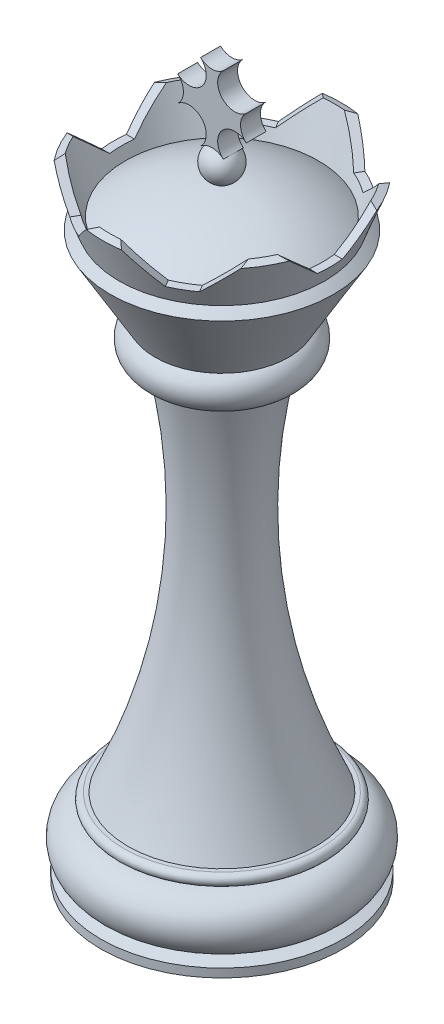
SolidWorks part; units mm, degrees
ref_plane "Front Plane" through (0, 0, 0) normal (0, 0, 1) x (1, 0, 0)
ref_plane "Top Plane" through (0, 0, 0) normal (0, 1, 0) x (1, 0, 0)
ref_plane "Right Plane" through (0, 0, 0) normal (1, 0, 0) x (0, 0, -1)
sketch "Sketch1" plane through (0, 0, 0) normal (0, 0, 1) x (1, 0, 0)
  line L0 (0, 0) -> (0, -19.2438) construction
  line L1 (0, 0) -> (12.5016, 0)
  line L2 (12.4781, -1.4284) -> (12.4781, -1.4919)
  line L3 (0, -9.6219) -> (15.4504, -9.6219)
  line L4 (15.4504, -9.6219) -> (15.4504, -8.5301)
  line L5 (15.4504, -8.5301) -> (13.8939, -8.0177)
  line L6 (0, 0) -> (0, -9.6219)
  line L7 (0, -9.6219) -> (0, 67.4601) construction
  line L8 (14.3355, 68.8883) -> (12.3128, 63.5994)
  line L9 (14.2366, 62.0928) -> (8.5232, 52.2861)
  line L10 (15.2333, 68.545) -> (13.1173, 63.0119)
  line L12 (0, 0) -> (0, -9.6219)
  line L13 (0, 67.4601) -> (0, 0)
  line L14 (14.2366, 62.0928) -> (0, 62.0928)
  line L18 (0, 67.4601) -> (0, 82.6937) construction
  line L19 (-24.4756, 76.1676) -> (25.7476, 76.1676) construction
  line L20 (0, 71.8293) -> (0, 64.3767)
  line L21 (14.3355, 68.8883) -> (15.2333, 68.545)
  arc A0 (12.5016, 0) -> (12.4781, -1.4284) centre (12.5016, -0.7144) cw
  arc A1 (13.8939, -8.0177) -> (12.4781, -1.4919) centre (12.4226, -4.9204) ccw
  arc A3 (8.5232, 52.2861) -> (6.8282, 47.8206) centre (7.3045, 50.1942) cw
  arc A4 (0, 67.4601) -> (14.2366, 62.0928) centre (0, 45.8952) cw
  arc A10 (6.8282, 47.8206) -> (11.9974, 0) centre (79.8437, 31.5237) ccw
  arc A21 (4.3733, 77.7991) -> (4.3733, 74.536) centre (5.8311, 76.1676) ccw
  arc A23 (-1.4578, 81.0622) -> (1.4578, 81.0622) centre (0, 82.6937) ccw
  arc A24 (-4.3733, 74.536) -> (-4.3733, 77.7991) centre (-5.8311, 76.1676) ccw
  arc A25 (-4.3733, 77.7991) -> (-1.4578, 81.0622) centre (-2.9156, 79.4307) ccw
  arc A26 (1.4578, 81.0622) -> (4.3733, 77.7991) centre (2.9156, 79.4307) ccw
  arc A27 (-1.4578, 71.273) -> (-4.3733, 74.536) centre (-2.9156, 72.9045) ccw
  arc A28 (4.3733, 74.536) -> (1.4578, 71.273) centre (2.9156, 72.9045) ccw
  arc A29 (1.4578, 71.273) -> (-1.4578, 71.273) centre (0, 69.6414) ccw
  arc A30 (0.162, 67.4595) -> (-1.4578, 71.273) centre (0, 69.6414) ccw
  dimension "D1" = 0.0635
  dimension "D4" = 0.7144
  dimension "D3" = 3.429
  dimension "D6" = 2.1879
  dimension "D2" = 12.5016
  dimension "D5" = 9.6219
revolve "Revolve1" add sketch "Sketch1" angle 360 about L0 region at (4.2323, 32.0823, 0) region at (7.4657, -4.9178, 0) region at (13.7536, 66.0113, 0)
sketch "Sketch8" plane through (0, 0, 0) normal (1, 0, 0) x (0, 0, -1)
  line L0 (-1.5923, 64.9743) -> (1.5923, 64.9743)
  line L1 (0, 72.9777) -> (0, -12.7055) construction
  line L2 (-1.5923, 64.9743) -> (-7.1168, 69.9256)
  line L3 (-7.1168, 69.9256) -> (7.1168, 69.9256)
  line L4 (7.1168, 69.9256) -> (1.5923, 64.9743)
  point P2 (-1.2255, 62.6893)
  point P4 (-4.334, 69.0416)
  point P8 (-7.1938, 68.1435)
  point P10 (-7.1168, 69.9256)
  point P11 (0, 0)
  point P12 (1.1861, 65.1127)
  point P13 (-1.5923, 64.9743)
extrude "Cut-Extrude2" cut sketch "Sketch8" along normal through all
pattern_circular "CirPattern1" count 6 over 360 about axis through (0, -9.6219, 0) along (0, 1, 0) of "Cut-Extrude2"
revolve "Revolve2" add sketch "Sketch1<10>" angle 360 about L18 region at (5.44, 64.2644, 0) region at (0.9287, 69.6416, 0)
sketch "Sketch1<10>" plane through (0, 0, 0) normal (0, 0, 1) x (1, 0, 0) same geometry as "Sketch1"
extrude "Boss-Extrude2" add sketch "Sketch1<11>" along normal mid plane 2.54 separate body contours A27 A24 A25 A23 A26 A21 A28 A29
sketch "Sketch1<11>" plane through (0, 0, 0) normal (0, 0, 1) x (1, 0, 0) same geometry as "Sketch1"
